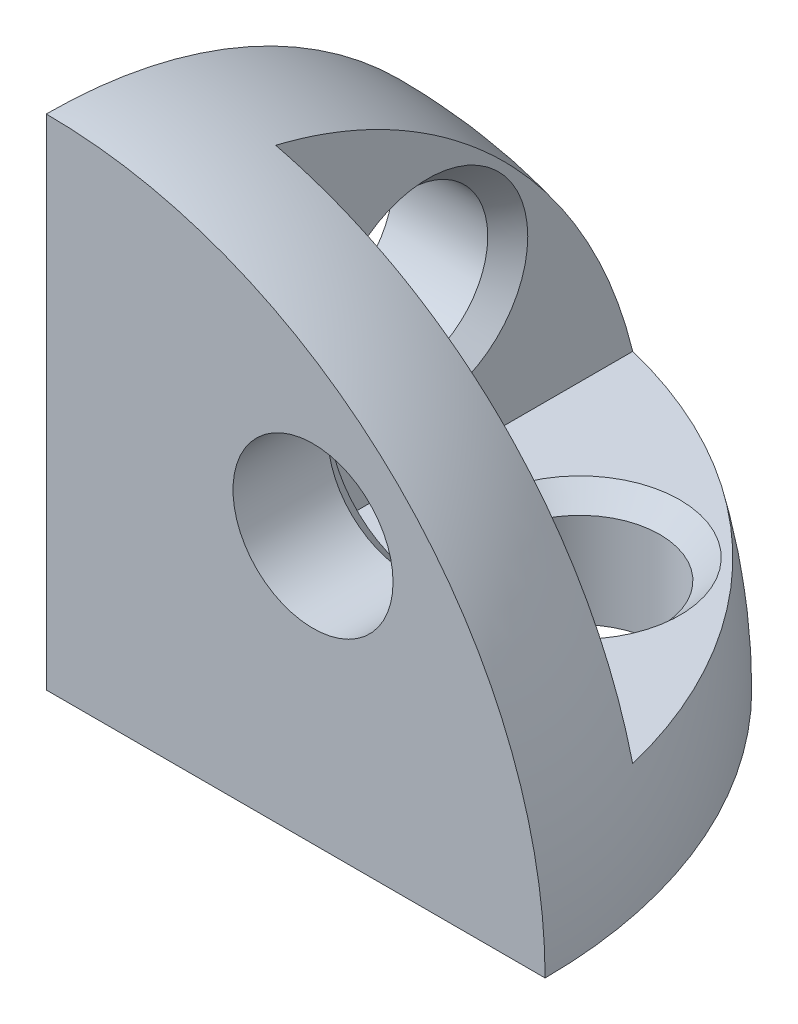
SolidWorks part; units mm, degrees
ref_plane "前视基准面" through (0, 0, 0) normal (0, 0, 1) x (1, 0, 0)
ref_plane "上视基准面" through (0, 0, 0) normal (0, 1, 0) x (1, 0, 0)
ref_plane "右视基准面" through (0, 0, 0) normal (1, 0, 0) x (0, 0, -1)
sketch "草图1" plane through (0, 0, 0) normal (0, 0, 1) x (1, 0, 0)
  line L0 (0, 0) -> (18.7, 0)
  line L1 (0, 0) -> (0, 18.7)
  line L2 (0, 0) -> (10, 0)
  arc A0 (18.7, 0) -> (0, 18.7) centre (0, 0) ccw
  circle A1 centre (10, 10) radius 3
  dimension "D1" = 10
revolve "旋转1" add sketch "草图1" angle 90 about L1 region at (7.6997, 7.6997, 0) region at (10, 10, 0)
shell "抽壳3" thickness 4.3 removed face at (8.8153, 8.8153, -8.8153)
extrude "切除-拉伸2" cut sketch "草图1<3>" against normal blind 10 contours A1 region at (10, 10, 0)
sketch "草图1<3>" plane through (0, 0, 0) normal (0, 0, 1) x (1, 0, 0) same geometry as "草图1"
sketch "草图3" plane through (0, 0, 0) normal (0, -1, 0) x (1, 0, 0)
  line L0 (0, 0) -> (10, 0) construction
  circle A0 centre (10, -10) radius 3
  dimension "D1" = 10
extrude "切除-拉伸3" cut sketch "草图3" against normal blind 10
sketch "草图4" plane through (0, 0, 0) normal (-1, 0, 0) x (0, 0, 1)
  line L0 (0, 0) -> (0, 10) construction
  line L1 (0, 0) -> (0, 18.7) construction
  circle A0 centre (-10, 10) radius 3
  dimension "D1" = 10
extrude "切除-拉伸4" cut sketch "草图4" against normal blind 10
chamfer "倒角1" distance 0.75 angle 45 3 edges at (13, 10, -4.3) (10, 4.3, -13) (4.3, 10, -13)
